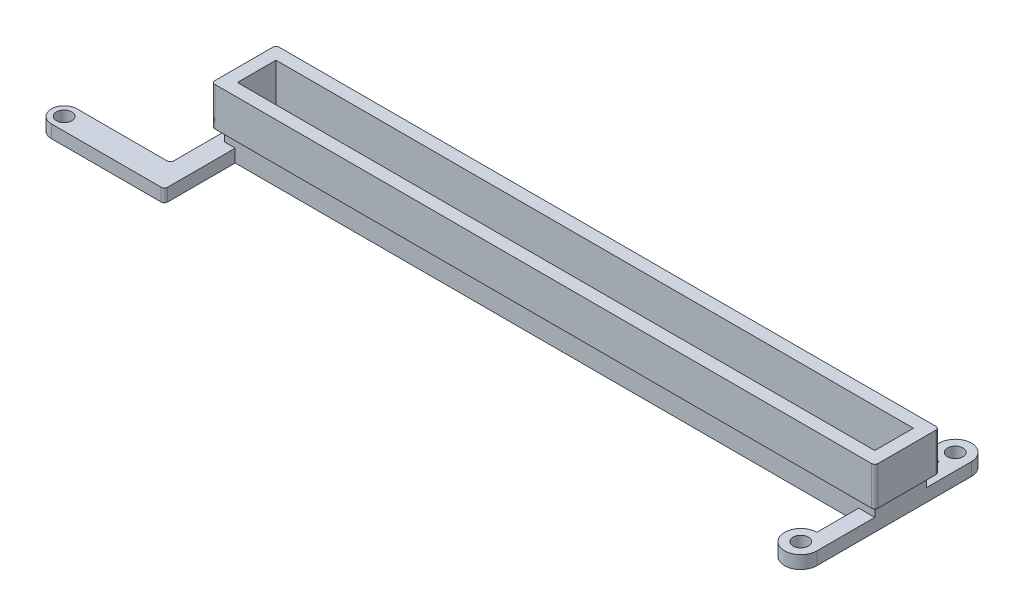
SolidWorks part; units mm, degrees
ref_plane "Front Plane" through (0, 0, 0) normal (0, 0, 1) x (1, 0, 0)
ref_plane "Top Plane" through (0, 0, 0) normal (0, 1, 0) x (1, 0, 0)
ref_plane "Right Plane" through (0, 0, 0) normal (1, 0, 0) x (0, 0, -1)
sketch "Sketch1" plane through (0, 0, 0) normal (0, 1, 0) x (1, 0, 0)
  line L0 (-50.5, 4) -> (-50.5, -4)
  line L1 (-49.5, 3) -> (49.5, 3)
  line L2 (-49.5, 3) -> (-49.5, -3)
  line L3 (-49.5, -3) -> (49.5, -3)
  line L4 (49.5, 3) -> (49.5, -3)
  line L5 (-49.5, 3) -> (49.5, -3) construction
  line L6 (-49.5, -3) -> (49.5, 3) construction
  line L7 (-50.5, -4) -> (50.5, -4)
  line L8 (50.5, 4) -> (50.5, -4)
  line L9 (-50.5, 4) -> (50.5, 4)
  point P0 (0, 0)
  dimension "D1" = 6
  dimension "D2" = 99
  dimension "D3" = 1
extrude "Boss-Extrude1" add sketch "Sketch1" along normal blind 10
sketch "Sketch2" plane through (0, 0, 0) normal (0, -1, 0) x (1, 0, 0)
  line L0 (0, 0) -> (74.3491, 0) construction
  line L1 (48, 0) -> (48, 10.5) construction
  line L2 (50.5, 4) -> (50.5, -4) construction
  line L4 (50.5, 4) -> (67.4224, 4) construction
  line L5 (50.5, -4) -> (69.4178, -4) construction
  line L7 (48, 4) -> (50.5, 4)
  line L9 (48, -4) -> (50.5, -4)
  line L11 (48, 0) -> (48, -8.5) construction
  line L15 (50.5, 4) -> (50.5, 13)
  line L16 (50.5, 13) -> (50, 13) construction
  line L17 (50.5, -4) -> (50.5, -11)
  line L18 (50.5, -11) -> (50, -11) construction
  line L19 (48, 10.5) -> (48, 4)
  line L20 (48, -8.5) -> (48, -4)
  line L21 (-50.5, 4) -> (-50.5, 13) construction
  line L22 (-50.5, 13) -> (-64.4, 13) construction
  line L23 (-66.4, 15) -> (-48.8351, 15)
  line L24 (-48.8351, 15) -> (-48.8351, 4)
  line L25 (-50.5, 4) -> (50.5, 4) construction
  line L26 (-66.4, 11) -> (-51.9017, 11)
  line L27 (-50.5, -4) -> (-59.3527, -4) construction
  line L28 (-51.9017, 11) -> (-51.9017, -4)
  line L29 (-51.9017, -4) -> (-50.5, -4)
  line L30 (-50.5, -4) -> (-50.5, 4)
  line L31 (-50.5, 4) -> (-48.8351, 4)
  line L32 (-64.4, 13) -> (-65.2, 13) construction
  line L33 (-65.2, 13) -> (-66.4, 13) construction
  line L34 (48, 10.5) -> (48, 11) construction
  line L35 (48, 11) -> (48, 13) construction
  line L36 (48, 11) -> (48, 10.5) construction
  line L37 (48, -8.5) -> (48, -9) construction
  line L38 (48, -9) -> (48, -11) construction
  line L39 (48, -9) -> (48, -8.5) construction
  circle A0 centre (48, 13) radius 1.2
  circle A4 centre (48, -11) radius 1.2
  arc A5 (50.5, -11) -> (48, -8.5) centre (48, -11) ccw construction
  arc A8 (48, 10.5) -> (50.5, 13) centre (48, 13) ccw construction
  circle A10 centre (-66.4, 13) radius 1.2
  arc A11 (-66.4, 15) -> (-66.4, 11) centre (-66.4, 13) ccw
  arc A12 (-64.4, 13) -> (-66.4, 15) centre (-66.4, 13) ccw construction
  arc A13 (-66.4, 11) -> (-64.4, 13) centre (-66.4, 13) ccw construction
  arc A14 (50.5, 13) -> (48, 10.5) centre (48, 13) ccw
  arc A15 (48, -8.5) -> (50.5, -11) centre (48, -11) ccw
  dimension "D3" = 2.4
  dimension "D9" = 2.4
  dimension "D10" = 4
  dimension "D1" = 2.5
  dimension "D2" = 13
  dimension "D5" = 11
  dimension "D7" = 9
  dimension "D8" = 15.9
extrude "Boss-Extrude2" add sketch "Sketch2" against normal blind 2
fillet "Fillet1" [suppressed] radius 2
fillet "Fillet2" [suppressed] radius 2
sketch "Sketch3" plane through (0, 10, 0) normal (0, 1, 0) x (1, 0, 0)
  line L0 (51.5, 5) -> (-51.5, 5)
  line L1 (-51.5, 5) -> (-51.5, -5)
  line L2 (-51.5, -5) -> (51.5, -5)
  line L3 (51.5, -5) -> (51.5, 5)
  line L4 (50.5, 4) -> (-50.5, 4)
  line L5 (-50.5, 4) -> (-50.5, -4)
  line L6 (-50.5, -4) -> (50.5, -4)
  line L7 (50.5, -4) -> (50.5, 4)
  line L8 (50.5, 4) -> (-50.5, 4)
  line L9 (-50.5, 4) -> (-50.5, -4)
  line L10 (-50.5, -4) -> (50.5, -4)
  line L11 (50.5, -4) -> (50.5, 4)
  dimension "D1" = 0
  dimension "D2" = 1
extrude "Boss-Extrude3" add sketch "Sketch3" against normal blind 6
fillet "Fillet3" [suppressed] radius 2
fillet "Fillet4" radius 1 1 edges at (0, 4, -4)
fillet "Fillet5" radius 1 1 edges at (0, 4, 4)
fillet "Fillet6" radius 1 1 edges at (50.5, 4, 0)
fillet "Fillet7" radius 1 1 edges at (-50.5, 4, 0)
fillet "Fillet8" radius 0.5 2 edges at (-48.8351, 1, 15) (-51.9017, 1, 11)
fillet "Fillet9" radius 0.5 4 edges at (51.5, 7, -5) (51.5, 7, 5) (-51.5, 7, 5) (-51.5, 7, -5)
